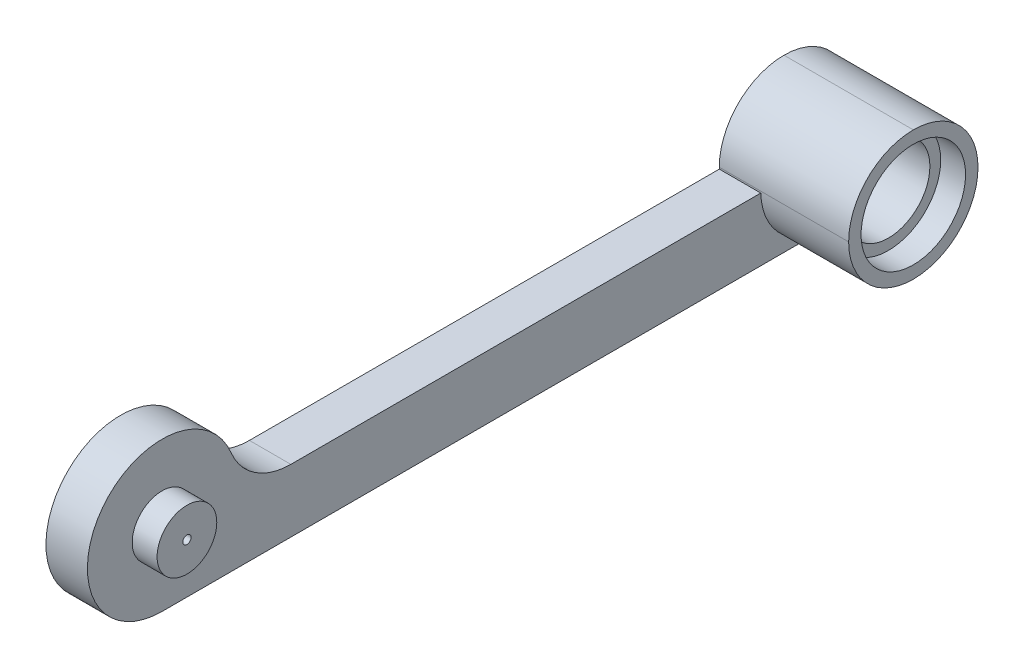
SolidWorks part; units mm, degrees
ref_plane "前视基准面" through (0, 0, 0) normal (0, 0, 1) x (1, 0, 0)
ref_plane "上视基准面" through (0, 0, 0) normal (0, 1, 0) x (1, 0, 0)
ref_plane "右视基准面" through (0, 0, 0) normal (1, 0, 0) x (0, 0, -1)
other "Configuration Table"
sketch "草图1" plane through (0, 0, 0) normal (1, 0, 0) x (0, 0, -1)
  line L0 (40, 3.3) -> (40, -4.5) construction
  line L1 (0, -4.5) -> (43.9, -4.5)
  line L2 (0, -4.5) -> (0, 3.3)
  line L3 (0, 3.3) -> (43.9, 3.3)
  line L4 (43.9, -4.5) -> (43.9, 3.3)
  line L6 (36.1, -4.5) -> (43.9, -4.5)
  line L7 (36.1, -4.5) -> (36.1, 3.3)
  line L8 (36.1, 3.3) -> (43.9, 3.3)
  line L9 (43.9, -4.5) -> (43.9, 3.3)
  line L10 (36.1, -4.5) -> (43.9, 3.3) construction
  line L11 (36.1, 3.3) -> (43.9, -4.5) construction
  circle A4 centre (0, 0) radius 1.8
  circle A5 centre (0, 0) radius 4.5
  circle A6 centre (40, -0.6) radius 2.5
  circle A7 centre (40, -0.6) radius 3.15
  circle A8 centre (0, 0) radius 0.25
  point P9 (40, -0.6)
  dimension "D1" = 3.6
  dimension "D4" = 40
  dimension "D5" = 3.9
  dimension "D2" = 9
  dimension "D6" = 5
  dimension "D7" = 6.3
  dimension "D8" = 0.5
  dimension "D3" = 7.8
extrude "凸台-拉伸1" add sketch "草图1" along normal blind 2.5 contours A5 | L3 L4 L1 L2
extrude "凸台-拉伸3" add sketch "草图1<6>" along normal blind 1.5 from surface contours L2 A4 | L2 A4 region at (0, 0, 0.7769) region at (0, 0, -0.7769) starting at face at (2.5, -0.0392, -21.2851)
sketch "草图1<6>" plane through (0, 0, 0) normal (1, 0, 0) x (0, 0, -1) same geometry as "草图1"
extrude "凸台-拉伸2" add sketch "草图1<5>" along normal blind 7.8 contours A6 | A7 A6 | L7 L1 L4 L3 A7 region at (0, -0.6, -36.2103) region at (0, -0.6, -40) region at (0, -0.6, -36.9391)
sketch "草图1<5>" plane through (0, 0, 0) normal (1, 0, 0) x (0, 0, -1) same geometry as "草图1"
extrude "切除-拉伸1" cut sketch "草图1<7>" along normal through all contours A6 region at (0, -0.6, -40)
sketch "草图1<7>" plane through (0, 0, 0) normal (1, 0, 0) x (0, 0, -1) same geometry as "草图1"
extrude "切除-拉伸2" cut sketch "草图1<8>" along normal blind 1.5 contours A7 A6 region at (0, -0.6, -36.9391)
sketch "草图1<8>" plane through (0, 0, 0) normal (1, 0, 0) x (0, 0, -1) same geometry as "草图1"
extrude "切除-拉伸3" cut sketch "草图1<9>" against normal blind 1.5 from surface contours A7 A6 region at (0, -0.6, -36.9391) starting at face at (7.8, -0.6, -42.5)
sketch "草图1<9>" plane through (0, 0, 0) normal (1, 0, 0) x (0, 0, -1) same geometry as "草图1"
sketch "草图2" plane through (0, 0, 0) normal (-1, 0, 0) x (0, 0, 1)
  line L0 (-3.0594, 3.3) -> (-43.9, 3.3) construction
  line L1 (-36.1, 3.3) -> (-4.5, 3.3)
  line L2 (-36.1, 3.3) -> (-36.1, -0.7)
  line L3 (-36.1, -0.7) -> (-4.5, -0.7)
  line L4 (-4.5, 3.3) -> (-4.5, -0.7)
  line L5 (-36.1, 3.3) -> (-36.1, -4.5) construction
  line L6 (-4.5, 3.3) -> (-3.0594, 3.3)
  arc A1 (0, -4.5) -> (-3.0594, 3.3) centre (0, 0) ccw construction
  circle A2 centre (0, 0) radius 4.5
  line M7 (-3.0594, 3.3) -> (-43.9, 3.3)
  dimension "D1" = 4
extrude "切除-拉伸4" cut sketch "草图2" against normal through all contours L4 L2 L3 M7 | A2 L4 M7 region at (0, 1.3, -20.3) region at (0, 2.5037, -4.083)
fillet "圆角1" radius 3.9 5 edges at (3.9, -4.5, -43.9) (3.9, 3.3, -43.9) (5.15, -4.5, -36.1) (3.9, 3.3, -36.1) (1.25, -0.7, -4.5)
ref_plane "基准面1" through (0, -10, 0) normal (0, 1, 0) x (1, 0, 0)
mirror "镜向2" about plane through (0, -10, 0) normal (0, 1, 0) of bodies 116 114
sketch "草图3" plane through (2.5, 0, 0) normal (1, 0, 0) x (0, 0, -1)
  line L1 (-11.0856, -9.8093) -> (53.6185, -9.8093)
  line L2 (-11.0856, -9.8093) -> (-11.0856, -30.7557)
  line L3 (-11.0856, -30.7557) -> (53.6185, -30.7557)
  line L4 (53.6185, -9.8093) -> (53.6185, -30.7557)
extrude "切除-拉伸5" cut sketch "草图3" against normal through all and the other way through all
